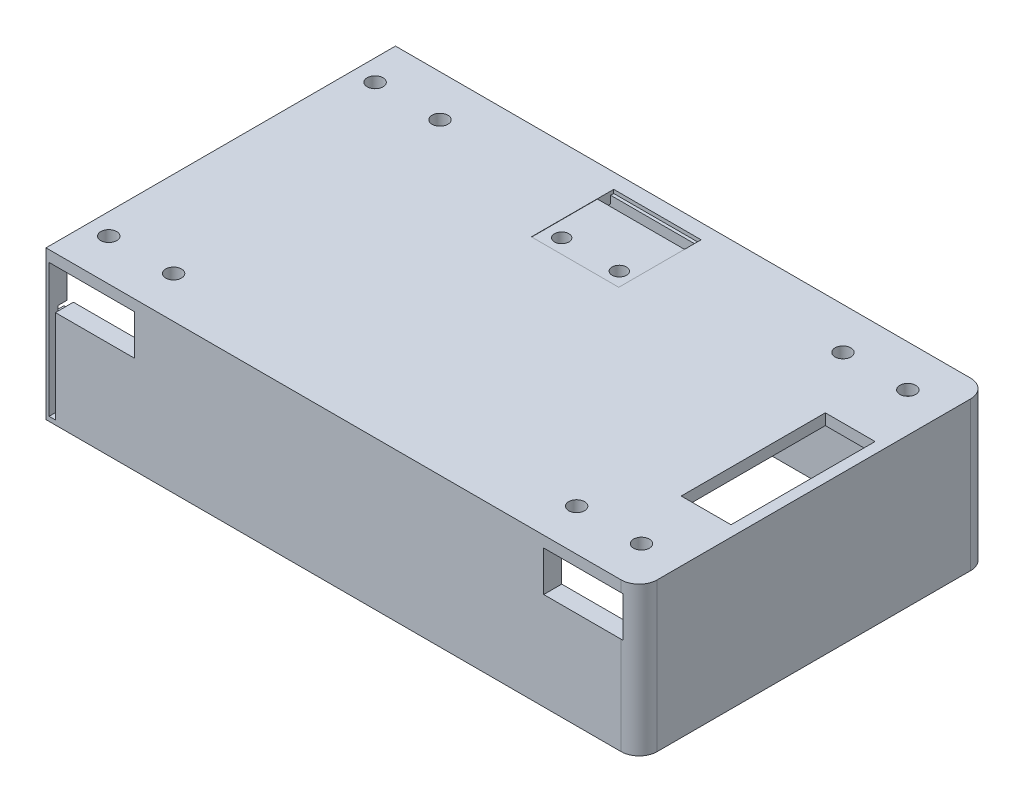
SolidWorks part; units mm, degrees
ref_plane "Alzado" through (0, 0, 0) normal (0, 0, 1) x (1, 0, 0)
ref_plane "Planta" through (0, 0, 0) normal (0, 1, 0) x (1, 0, 0)
ref_plane "Vista lateral" through (0, 0, 0) normal (1, 0, 0) x (0, 0, -1)
sketch "Croquis1" plane through (0, 0, 0) normal (0, 0, 1) x (1, 0, 0)
  line L0 (-8.5, 0) -> (8.5, 0) construction
  line L2 (57, 8.2) -> (57, -26)
  line L3 (57, -26) -> (-57, -26)
  line L4 (-57, 8.2) -> (-57, -26)
  line L5 (30.4, -16) -> (15.6, -16) construction
  line L7 (57, 8.2) -> (-57, 8.2)
  line L8 (47, 0) -> (47, -16) construction
  arc A0 (35, 3.2) -> (34, 3.2) centre (34.5, 3.2) ccw construction
  point P0 (0, 0)
  dimension "D1" = 5
  dimension "D2" = 10
  dimension "D3" = 10
extrude "Saliente-Extruir1" add sketch "Croquis1" against normal blind 97
shell "Vaciado1" thickness 5 removed face at (0, -26, -48.5)
sketch "Croquis2" plane through (0, 0, -97) normal (0, 0, -1) x (-1, 0, 0)
  line L0 (57, 8.2) -> (67.3347, 8.2)
  line L1 (67.3347, 8.2) -> (67.3347, -3.9674)
  line L2 (71.8143, 8.2) -> (71.8143, 10.2965)
  line L3 (67.3347, -26) -> (57, -26)
  line L4 (57, 8.2) -> (57, -26) construction
  line L5 (67.3347, -3.9674) -> (57, -3.9674)
  line L6 (67.3347, 8.2) -> (71.8143, 8.2)
  line L7 (71.8143, 8.2) -> (71.8143, -26)
  line L8 (71.8143, -26) -> (67.3347, -26)
  line L9 (0, 8.2) -> (0, -26) construction
  line L10 (-57, 8.2) -> (57, 8.2) construction
  line L11 (57, -26) -> (-57, -26) construction
  line L12 (71.8143, 10.2965) -> (-71.8143, 10.2965)
  line L13 (67.3347, 8.2) -> (-67.3347, 8.2)
  line L14 (-71.8143, -26) -> (-67.3347, -26)
  line L15 (-71.8143, 8.2) -> (-71.8143, -26)
  line L16 (-67.3347, 8.2) -> (-71.8143, 8.2)
  line L17 (-67.3347, -3.9674) -> (-57, -3.9674)
  line L18 (-67.3347, -26) -> (-57, -26)
  line L19 (-71.8143, 8.2) -> (-71.8143, 10.2965)
  line L20 (-67.3347, 8.2) -> (-67.3347, -3.9674)
  line L21 (-57, 8.2) -> (-67.3347, 8.2)
  point P21 (0, 10.2965)
  line M5 (57, -26) -> (57, 8.2)
  line M6 (57, 8.2) -> (-57, 8.2)
  line M7 (-57, 8.2) -> (-57, -26)
extrude "Saliente-Extruir2" add sketch "Croquis2" against normal through all contours L8 L7 L6 L1 L5 L3 M5 | L19 L16 L13 L0 L6 L2 L12 M6 | L20 L16 L15 L14 L18 L17 M7 region at (0, 9.2483, -97) region at (-65.1466, -12.5368, -97) region at (65.1466, -12.5368, -97)
sketch "Croquis3" plane through (0, -26, 0) normal (0, -1, 0) x (1, 0, 0)
  line L0 (0, 0) -> (0, -97) construction
  line L1 (-71.8143, 0) -> (71.8143, 0) construction
  line L2 (-71.8143, -97) -> (71.8143, -97) construction
  line L3 (-52, -5) -> (-71.8143, -5)
  line L4 (-71.8143, 0) -> (-71.8143, -97) construction
  line L5 (-52, -92) -> (-52, -5) construction
  line L6 (-68.8143, -68.5) -> (-55, -68.5)
  line L7 (-68.8143, -68.5) -> (-68.8143, -28.5)
  line L8 (-68.8143, -28.5) -> (-55, -28.5)
  line L9 (-55, -68.5) -> (-55, -28.5)
  line L10 (-68.8143, -68.5) -> (-55, -28.5) construction
  line L11 (-68.8143, -28.5) -> (-55, -68.5) construction
  line L12 (-71.8143, -48.5) -> (71.8143, -48.5) construction
  line L13 (71.8143, 0) -> (71.8143, -97) construction
  line L14 (68.8143, -28.5) -> (55, -68.5) construction
  line L15 (68.8143, -68.5) -> (55, -28.5) construction
  line L16 (55, -68.5) -> (55, -28.5)
  line L17 (68.8143, -28.5) -> (55, -28.5)
  line L18 (68.8143, -68.5) -> (68.8143, -28.5)
  line L19 (68.8143, -68.5) -> (55, -68.5)
  point P11 (-61.9071, -48.5)
  point P28 (61.9071, -48.5)
  dimension "D1" = 3
  dimension "D2" = 3
  dimension "D3" = 40
extrude "Cortar-Extruir1" cut sketch "Croquis3" against normal up to next contours L6 L9 L8 L7 | L19 L18 L17 L16 region at (-61.9071, -26, -48.5) region at (61.9071, -26, -48.5)
fillet "Redondeo2" radius 5 4 edges at (71.8143, -7.8517, -97) (-71.8143, -7.8517, -97) (71.8143, -7.8517, 0) (-71.8143, -7.8517, 0)
sketch "Croquis5" plane through (-71.8143, 0, 0) normal (-1, 0, 0) x (0, 0, 1)
  line L0 (-5, -10.6991) -> (2.7, -10.6991)
  line L2 (-5, -26) -> (-5, 10.2965) construction
  line L3 (2.7, -10.6991) -> (2.7, -23.7895)
  line L4 (2.7, -23.7895) -> (-5, -23.7895)
  line L5 (-5, -23.7895) -> (-5, -10.6991)
  line L6 (-48.5, -26) -> (-48.5, 10.2965) construction
  line L7 (-5, -26) -> (-92, -26) construction
  line L8 (-5, 10.2965) -> (-92, 10.2965) construction
  line L9 (-92, -23.7895) -> (-92, -10.6991)
  line L10 (-92, -10.6991) -> (-99.7, -10.6991)
  line L11 (-99.7, -10.6991) -> (-99.7, -23.7895)
  line L12 (-99.7, -23.7895) -> (-92, -23.7895)
sketch "Croquis6" plane through (0, 0, -97) normal (0, 0, -1) x (-1, 0, 0)
  line L0 (-67.3347, 8.2) -> (-57, -3.9674) construction
  line L1 (67.3347, 8.2) -> (57, -3.9674) construction
  line L2 (-60.6173, 0) -> (60.6173, 0)
  line L3 (-60.6173, 8.2) -> (-60.6173, -3.9674) construction
  line L4 (-57, 8.2) -> (-66.8143, 8.2) construction
  line L5 (-66.8143, -3.9674) -> (-57, -3.9674) construction
  line L6 (60.6173, 8.2) -> (60.6173, -3.9674) construction
  line L7 (66.8143, 8.2) -> (57, 8.2) construction
  line L8 (66.8143, -3.9674) -> (57, -3.9674) construction
  line L9 (0, 10.2965) -> (0, -26) construction
  line L10 (-66.7673, -3.0837) -> (-54.4673, -3.0837)
  line L11 (-66.7673, -3.0837) -> (-66.7673, 7.3163)
  line L12 (-66.7673, 7.3163) -> (-54.4673, 7.3163)
  line L13 (-54.4673, -3.0837) -> (-54.4673, 7.3163)
  line L14 (-60.6173, 7.3163) -> (-60.6173, -3.0837) construction
  line L15 (-66.7673, 2.1163) -> (-54.4673, 2.1163) construction
  line L16 (66.8143, 10.2965) -> (-66.8143, 10.2965) construction
  line L17 (66.8143, -26) -> (-66.8143, -26) construction
  line L18 (66.7673, 2.1163) -> (54.4673, 2.1163) construction
  line L19 (60.6173, 7.3163) -> (60.6173, -3.0837) construction
  line L20 (60.6173, 8.2) -> (60.6173, -3.9674) construction
  line L21 (67.3347, 8.2) -> (57, -3.9674) construction
  line L22 (54.4673, -3.0837) -> (54.4673, 7.3163)
  line L23 (66.7673, 7.3163) -> (54.4673, 7.3163)
  line L24 (66.7673, -3.0837) -> (66.7673, 7.3163)
  line L25 (66.7673, -3.0837) -> (54.4673, -3.0837)
  point P8 (62.1673, 2.1163)
  point P14 (0, 0)
  point P28 (-60.6173, 2.1163)
  point P46 (60.6173, 2.1163)
  dimension "D1" = 1.55
  dimension "D2" = 12.3
  dimension "D3" = 10.4
extrude "Cortar-Extruir3" cut sketch "Croquis6" against normal through all contours L22 L23 L24 L25 | L11 L12 L13 L10
sketch "Croquis7" plane through (0, 0, -97) normal (0, 0, -1) x (-1, 0, 0)
  line L0 (-57, 7.3163) -> (-57, 8.2)
  line L1 (-54.4673, -3.0837) -> (-66.6673, -3.0837)
  line L2 (-54.4673, -3.0837) -> (-54.4673, 7.325)
  line L3 (-54.4673, 7.325) -> (-66.6673, 7.325)
  line L4 (-66.6673, -3.0837) -> (-66.6673, 7.325)
  line L5 (-57, 8.2) -> (-67.3347, 8.2)
  line L6 (-67.3347, 8.2) -> (-67.3347, -3.9674)
  line L7 (-67.3347, -3.9674) -> (-57, -3.9674)
  line L8 (-57, -3.9674) -> (-57, -3.0837)
  line L9 (57, 7.3163) -> (57, 8.2)
  line L10 (54.4673, -3.0837) -> (66.6673, -3.0837)
  line L11 (54.4673, -3.0837) -> (54.4673, 7.3163)
  line L12 (54.4673, 7.3163) -> (66.6673, 7.3163)
  line L13 (66.6673, -3.0837) -> (66.6673, 7.3163)
  line L14 (57, 8.2) -> (67.3347, 8.2)
  line L15 (67.3347, 8.2) -> (67.3347, -3.9674)
  line L16 (67.3347, -3.9674) -> (57, -3.9674)
  line L17 (57, -3.9674) -> (57, -3.0837)
  line M3 (57, -3.9674) -> (57, -3.0837)
  line M7 (57, 7.3163) -> (57, 8.2)
  line M8 (57, 8.2) -> (66.8143, 8.2)
  line M12 (-66.8143, 8.2) -> (-57, 8.2)
  line M13 (-57, 8.2) -> (-57, 7.3163)
  line M17 (-57, -3.0837) -> (-57, -3.9674)
  line M18 (-57, -3.9674) -> (-66.8143, -3.9674)
  line M22 (66.8143, -3.9674) -> (57, -3.9674)
  dimension "D1" = 12.2
  dimension "D2" = 12.2
extrude "Saliente-Extruir3" add sketch "Croquis7" against normal through all contours L16 L15 L14 L12 L13 L10 M8 M7 M3 M22 | L6 L7 L1 L4 L3 L5 M18 M17 M13 M12 region at (61.8337, 7.4847, -97) region at (-57.1596, 7.7582, -97)
sketch "Croquis8" plane through (0, 10.2965, 0) normal (0, 1, 0) x (1, 0, 0)
  line L1 (-68.8143, 68.5) -> (-55, 68.5)
  line L2 (-68.8143, 68.5) -> (-68.8143, 28.5)
  line L3 (-68.8143, 28.5) -> (-55, 28.5)
  line L4 (-55, 68.5) -> (-55, 28.5)
  line L5 (55, 68.5) -> (68.8143, 68.5)
  line L6 (55, 68.5) -> (55, 28.5)
  line L7 (55, 28.5) -> (68.8143, 28.5)
  line L8 (68.8143, 68.5) -> (68.8143, 28.5)
extrude "Cortar-Extruir4" cut sketch "Croquis8" against normal through all
sketch "Croquis9" plane through (0, 3.2, 0) normal (0, -1, 0) x (1, 0, 0)
  line L0 (52, -92) -> (52, -5) construction
  line L1 (-52, -5) -> (52, -5)
  line L2 (-52, -5) -> (-52, -92)
  line L3 (-52, -92) -> (52, -92)
  line L4 (52, -5) -> (52, -92)
extrude "Cortar-Extruir5" cut sketch "Croquis9" against normal blind 10
ref_plane "Plano1" through (54.4673, -3.0837, -97) normal (-1, 0, 0) x (0, 0, 1)
sketch "Croquis11" plane through (0, -26, 0) normal (0, -1, 0) x (1, 0, 0)
  line L1 (55, -28.5) -> (53.5, -28.5)
  line L2 (55, -28.5) -> (55, -68.4995)
  line L3 (55, -68.4995) -> (53.5, -68.4995)
  line L4 (53.5, -28.5) -> (53.5, -68.4995)
  line L5 (-55, -68.5) -> (-53.5, -68.5)
  line L6 (-55, -68.5) -> (-55, -28.5)
  line L7 (-55, -28.5) -> (-53.5, -28.5)
  line L8 (-53.5, -68.5) -> (-53.5, -28.5)
  dimension "D1" = 1.5
  dimension "D2" = 1.5
extrude "Cortar-Extruir6" cut sketch "Croquis11" against normal up to vertex (33.3163 mm away) up to point (-55, 7.3163, -28.5)
sketch "Croquis13" plane through (0, -26, 0) normal (0, -1, 0) x (1, 0, 0)
  line L1 (-68.8143, -28.5) -> (-53.5, -28.5)
  line L2 (-68.8143, -28.5) -> (-68.8143, -24)
  line L3 (-68.8143, -24) -> (-53.5, -24)
  line L4 (-53.5, -28.5) -> (-53.5, -24)
  line L5 (-68.8143, -68.5) -> (-53.5, -68.5)
  line L6 (-68.8143, -68.5) -> (-68.8143, -73)
  line L7 (-68.8143, -73) -> (-53.5, -73)
  line L8 (-53.5, -68.5) -> (-53.5, -73)
  line L9 (53.5, -28.5) -> (68.8143, -28.5)
  line L10 (53.5, -28.5) -> (53.5, -24)
  line L11 (53.5, -24) -> (68.8143, -24)
  line L12 (68.8143, -28.5) -> (68.8143, -24)
  line L13 (53.5, -68.4995) -> (68.8143, -68.4995)
  line L14 (53.5, -68.4995) -> (53.5, -72.9995)
  line L15 (53.5, -72.9995) -> (68.8143, -72.9995)
  line L16 (68.8143, -68.4995) -> (68.8143, -72.9995)
  dimension "D1" = 4.5
  dimension "D2" = 4.5
  dimension "D3" = 4.5
  dimension "D4" = 4.5
extrude "Cortar-Extruir7" cut sketch "Croquis13" against normal up to surface (33.3163 mm away) up to face at (-58.4616, 7.3163, -48.5)
sketch "Croquis14" plane through (-55, 0, 0) normal (-1, 0, 0) x (0, 0, 1)
  line L4 (-68.5, 10.2965) -> (-68.5, 7.3163)
  line L5 (-68.5, 7.3163) -> (-28.5, 7.3163)
  line L6 (-28.5, 7.3163) -> (-28.5, 10.2965)
  line L7 (-28.5, 10.2965) -> (-68.5, 10.2965)
  line L8 (-68.5, 10.2965) -> (-68.5, 7.3163)
  line L9 (-68.5, 7.3163) -> (-28.5, 7.3163)
  line L10 (-28.5, 7.3163) -> (-28.5, 10.2965)
  line L11 (-28.5, 10.2965) -> (-68.5, 10.2965)
  dimension "D1" = 0
extrude "Saliente-Extruir4" add sketch "Croquis14" along normal blind 15.4989
sketch "Croquis16" plane through (-71.8143, 0, 0) normal (-1, 0, 0) x (0, 0, 1)
  line L0 (-5, 10.2965) -> (-98.4159, 10.2965)
  line L1 (-98.4159, 10.2965) -> (-98.4159, -27.1379)
  line L2 (-98.4159, -27.1379) -> (0, -27.1379)
  line L3 (0, -27.1379) -> (0, 10.2965)
  line L4 (0, 10.2965) -> (-5, 10.2965)
extrude "Cortar-Extruir8" cut sketch "Croquis16" against normal blind 20.4989
sketch "Croquis19" plane through (-51.3154, 0, 0) normal (-1, 0, 0) x (0, 0, 1)
  line L0 (0, -4.4636) -> (-5, -4.4636)
  line L1 (-92, -4.4636) -> (-97, -4.4636)
  line L2 (-5, -26) -> (-5, 10.2965) construction
  line L3 (0, 10.2965) -> (-5, 10.2965)
  line L4 (0, -26) -> (0, 10.2965)
  line L5 (0, 10.2965) -> (-5, 10.2965)
  line L6 (-5, 10.2965) -> (-5, -26)
  line L7 (-5, -26) -> (0, -26)
  line L8 (0, -26) -> (0, -4.4636)
  line L10 (-5, -4.4636) -> (-5, -26)
  line L11 (-5, -26) -> (0, -26)
  line L12 (0, 10.2965) -> (0, 7.9471)
  line L13 (-97, -26) -> (-92, -26)
  line L14 (-92, -26) -> (-92, 10.2965)
  line L15 (-92, 10.2965) -> (-97, 10.2965)
  line L16 (-97, 10.2965) -> (-97, -26)
  line L17 (-97, -26) -> (-92, -26)
  line L18 (-92, -26) -> (-92, -4.4636)
  line L20 (-97, -4.4636) -> (-97, -26)
  line L21 (0, 7.9471) -> (-5, 7.9471)
  line L22 (-5, 10.2965) -> (-5, 7.9471)
  line L23 (-97, -26) -> (-97, 10.2965) construction
  line L24 (-92, 10.2965) -> (-97, 10.2965)
  line L25 (-92, 10.2965) -> (-92, 7.9471)
  line L26 (-92, 7.9471) -> (-97, 7.9471)
  line L27 (-97, 10.2965) -> (-97, 7.9471)
  dimension "D1" = 0
  dimension "D2" = 0
extrude "Saliente-Extruir5" add sketch "Croquis19" along normal blind 22
sketch "Croquis20" plane through (-73.3154, 0, 0) normal (-1, 0, 0) x (0, 0, 1)
  line L0 (-5, -26) -> (0, -26) construction
  line L1 (0, 10.2965) -> (-5, 10.2965)
  line L2 (0, 10.2965) -> (0, -26)
  line L3 (0, -26) -> (-5, -26)
  line L4 (-5, 10.2965) -> (-5, -26)
  line L5 (-5, -4.4636) -> (-5, -26) construction
  line L7 (-92, 10.2965) -> (-97, 10.2965)
  line L8 (-92, 10.2965) -> (-92, -26)
  line L9 (-92, -26) -> (-97, -26)
  line L10 (-97, 10.2965) -> (-97, -26)
extrude "Saliente-Extruir6" add sketch "Croquis20" along normal blind 19.5
sketch "Croquis21" plane through (52, 0, 0) normal (-1, 0, 0) x (0, 0, 1)
  line L1 (-5, 10.2965) -> (-92, 10.2965)
  line L2 (-5, 10.2965) -> (-5, 7.9471)
  line L3 (-5, 7.9471) -> (-92, 7.9471)
  line L4 (-92, 10.2965) -> (-92, 7.9471)
extrude "Saliente-Extruir7" add sketch "Croquis21" along normal up to surface (144.8154 mm away) up to face at (-92.8154, -7.8517, -2.5)
sketch "Croquis23" plane through (0, 0, 0) normal (0, 0, 1) x (1, 0, 0)
  line L0 (-92.8154, 10.2965) -> (-92.8154, 7.8837) construction
  line L1 (-92.8154, -26) -> (-92.8154, 10.2965) construction
  line L3 (-92.3813, 9.0724) -> (-90.9831, 9.0724)
  line L4 (-92.3813, 9.0724) -> (-92.3813, -24.6285)
  line L5 (-92.3813, -24.6285) -> (-90.9831, -24.6285)
  line L6 (-90.9831, 9.0724) -> (-90.9831, -24.6285)
extrude "Cortar-Extruir9" cut sketch "Croquis23" against normal blind 95.5
sketch "Croquis24" plane through (0, 10.2965, 0) normal (0, 1, 0) x (1, 0, 0)
  line L0 (-92.8154, 48.5) -> (-89.7623, 48.5) construction
  line L1 (-92.8154, 0) -> (-92.8154, 97) construction
  line L2 (-89.7623, 37.3943) -> (-89.7623, 59.6057)
  line L3 (-89.7623, 59.6057) -> (-67.2686, 59.6057)
  line L4 (-67.2686, 59.6057) -> (-67.2686, 37.3943)
  line L5 (-67.2686, 37.3943) -> (-89.7623, 37.3943)
  point P7 (-89.7623, 48.5)
extrude "Cortar-Extruir10" cut sketch "Croquis24" against normal blind 1.5
sketch "Croquis25" plane through (0, 8.7965, 0) normal (0, 1, 0) x (1, 0, 0)
  line L0 (-89.7623, 59.6057) -> (-89.7623, 37.3943) construction
  line L1 (-89.7623, 40.2654) -> (-84.2178, 40.2654)
  line L2 (-89.7623, 40.2654) -> (-89.7623, 57.0137)
  line L3 (-89.7623, 57.0137) -> (-84.2178, 57.0137)
  line L4 (-84.2178, 40.2654) -> (-84.2178, 57.0137)
extrude "Cortar-Extruir11" cut sketch "Croquis25" against normal blind 1.5
sketch "Croquis26" plane through (-89.7623, 0, 0) normal (1, 0, 0) x (0, 0, -1)
  line L8 (59.6057, 10.2965) -> (37.3943, 10.2965)
  line L9 (37.3943, 10.2965) -> (37.3943, 8.7965)
  line L10 (37.3943, 8.7965) -> (40.2654, 8.7965)
  line L11 (40.2654, 8.7965) -> (40.2654, 7.9471)
  line L12 (40.2654, 7.9471) -> (57.0137, 7.9471)
  line L13 (57.0137, 7.9471) -> (57.0137, 8.7965)
  line L14 (57.0137, 8.7965) -> (59.6057, 8.7965)
  line L15 (59.6057, 8.7965) -> (59.6057, 10.2965)
  line L16 (59.6057, 10.2965) -> (37.3943, 10.2965)
  line L17 (37.3943, 10.2965) -> (37.3943, 8.7965)
  line L18 (37.3943, 8.7965) -> (40.2654, 8.7965)
  line L19 (40.2654, 8.7965) -> (40.2654, 7.9471)
  line L20 (40.2654, 7.9471) -> (57.0137, 7.9471)
  line L21 (57.0137, 7.9471) -> (57.0137, 8.7965)
  line L22 (57.0137, 8.7965) -> (59.6057, 8.7965)
  line L23 (59.6057, 8.7965) -> (59.6057, 10.2965)
  dimension "D1" = 0
extrude "Saliente-Extruir8" add sketch "Croquis26" along normal blind 46
sketch "Croquis27" plane through (0, 10.2965, 0) normal (0, 1, 0) x (1, 0, 0)
  line L0 (-90.9831, 92) -> (-73.3154, 92) construction
  line L1 (-82.5488, 92) -> (-60.5488, 92)
  line L2 (-82.5488, 92) -> (-82.5488, 70)
  line L3 (-82.5488, 70) -> (-60.5488, 70)
  line L4 (-60.5488, 92) -> (-60.5488, 70)
  dimension "D1" = 22
  dimension "D2" = 22
extrude "Cortar-Extruir12" cut sketch "Croquis27" against normal blind 1
sketch "Croquis28" plane through (0, 9.2965, 0) normal (0, 1, 0) x (1, 0, 0)
  line L1 (-60.9342, 91.7) -> (-82.0403, 91.7)
  line L2 (-60.9342, 91.7) -> (-60.9342, 87.3693)
  line L3 (-60.9342, 87.3693) -> (-82.0403, 87.3693)
  line L4 (-82.0403, 91.7) -> (-82.0403, 87.3693)
extrude "Cortar-Extruir14" cut sketch "Croquis28" against normal blind 1.5
sketch "Croquis29" plane through (-90.9831, 0, 0) normal (-1, 0, 0) x (0, 0, 1)
  line L8 (-92, 7.9471) -> (-5, 7.9471)
  line L9 (-5, 7.9471) -> (-5, -24.6285)
  line L10 (-5, -24.6285) -> (0, -24.6285)
  line L11 (0, -24.6285) -> (0, 9.0724)
  line L12 (0, 9.0724) -> (-95.5, 9.0724)
  line L13 (-95.5, 9.0724) -> (-95.5, -24.6285)
  line L14 (-95.5, -24.6285) -> (-92, -24.6285)
  line L15 (-92, -24.6285) -> (-92, 7.9471)
  line L16 (-92, 7.9471) -> (-5, 7.9471)
  line L17 (-5, 7.9471) -> (-5, -24.6285)
  line L18 (-5, -24.6285) -> (0, -24.6285)
  line L19 (0, -24.6285) -> (0, 9.0724)
  line L20 (0, 9.0724) -> (-95.5, 9.0724)
  line L21 (-95.5, 9.0724) -> (-95.5, -24.6285)
  line L22 (-95.5, -24.6285) -> (-92, -24.6285)
  line L23 (-92, -24.6285) -> (-92, 7.9471)
  dimension "D1" = 0
extrude "Saliente-Extruir9" add sketch "Croquis29" along normal up to surface (1.8323 mm away) up to face at (-92.8154, -8.4391, -48.5)
sketch "Croquis30" plane through (0, 7.9471, 0) normal (0, -1, 0) x (1, 0, 0)
  line L0 (-26.9383, -87.6693) -> (-5.8322, -87.6693)
  line L1 (-82.0403, -87.3693) -> (-60.9342, -87.3693)
  line L2 (-82.0403, -87.3693) -> (-82.0403, -91.7)
  line L3 (-82.0403, -91.7) -> (-60.9342, -91.7)
  line L4 (-60.9342, -87.3693) -> (-60.9342, -91.7)
  line L6 (-26.9383, -92) -> (-5.8322, -92)
  line L8 (-51.3154, -92) -> (52, -92) construction
  line L9 (-26.9383, -92) -> (-26.9383, -87.6693)
  line L10 (-5.8322, -87.6693) -> (-5.8322, -92)
extrude "Cortar-Extruir15" cut sketch "Croquis30" against normal blind 10
sketch "Croquis31" plane through (0, 10.2965, 0) normal (0, 1, 0) x (1, 0, 0)
  line L1 (-82.5488, 92) -> (-60.5488, 92)
  line L2 (-82.5488, 92) -> (-82.5488, 70)
  line L3 (-82.5488, 70) -> (-60.5488, 70)
  line L4 (-60.5488, 92) -> (-60.5488, 70)
  line L5 (-28.087, 92.8509) -> (-3.838, 92.8509)
  line L6 (-28.087, 92.8509) -> (-28.087, 70)
  line L7 (-28.087, 70) -> (-3.838, 70)
  line L8 (-3.838, 92.8509) -> (-3.838, 70)
  dimension "D1" = 22
  dimension "D2" = 22
extrude "Cortar-Extruir16" cut sketch "Croquis31" against normal blind 1
sketch "Croquis32" plane through (0, 7.9471, 0) normal (0, -1, 0) x (1, 0, 0)
  line L0 (-92.8154, -92) -> (-73.3154, -92) construction
  line L1 (-83.0654, -92) -> (-55.1323, -92)
  line L2 (-83.0654, -92) -> (-83.0654, -55.3525)
  line L3 (-83.0654, -55.3525) -> (-55.1323, -55.3525)
  line L4 (-55.1323, -92) -> (-55.1323, -55.3525)
extrude "Saliente-Extruir10" add sketch "Croquis32" against normal up to surface (2.3495 mm away) up to face at (-15.9625, 10.2965, -81.4255)
sketch "Croquis33" plane through (0, 7.9471, 0) normal (0, -1, 0) x (1, 0, 0)
  line L0 (52, -5) -> (-92.8154, -5)
  dimension "D1" = 144.8154
sketch "Croquis36" plane through (-92.8154, 0, 0) normal (-1, 0, 0) x (0, 0, 1)
  line L8 (-94.5, -6.1159) -> (-94.5, -4.3783) construction
  line L18 (-2.5, -6.1159) -> (-2.5, -4.3783) construction
  line L21 (-2.5, -6.1159) -> (-94.5, -6.1159)
  line L26 (-2.5, -6.1159) -> (-94.5, -6.1159)
  line L30 (-2.5, -6.1159) -> (-2.5, -4.3783)
  line L31 (-2.5, -4.3783) -> (-94.5, -4.3783)
  line L32 (-94.5, -6.1159) -> (-94.5, -4.3783)
  line M11 (-92, -26) -> (-92, 7.9471)
  line M13 (-5, 7.9471) -> (-5, -26)
extrude "Cortar-Extruir17" cut sketch "Croquis36" against normal blind 147 contours L31 L21 M13 M11 | L30 L31 L21 M13 | L32 L21 L31 M11 region at (-92.8154, -5.2471, -3.75) region at (-92.8154, -5.2471, -48.5) region at (-92.8154, -5.2471, -93.25)
sketch "Croquis37" plane through (0, -26, 0) normal (0, -1, 0) x (1, 0, 0)
  line L0 (68.8143, -24) -> (53.5, -24) construction
  line L1 (53.5, -24) -> (53.5, -72.9995) construction
  line L2 (53.5, -72.9995) -> (68.8143, -72.9995) construction
  line L3 (68.8143, -72.9995) -> (68.8143, -24) construction
  line L4 (68.8143, -24) -> (53.5, -24)
  line L5 (53.5, -24) -> (53.5, -72.9995)
  line L6 (53.5, -72.9995) -> (68.8143, -72.9995)
  line L7 (68.8143, -72.9995) -> (68.8143, -24)
  line L8 (66.8143, 0) -> (-92.8154, 0)
  line L9 (-92.8154, 0) -> (-92.8154, -5)
  line L10 (-92.8154, -5) -> (52, -5)
  line L11 (52, -5) -> (52, -92)
  line L12 (52, -92) -> (-92.8154, -92)
  line L13 (-92.8154, -92) -> (-92.8154, -97)
  line L14 (-92.8154, -97) -> (66.8143, -97)
  line L15 (71.8143, -92) -> (71.8143, -5)
  line L16 (66.8143, 0) -> (-92.8154, 0)
  line L17 (-92.8154, 0) -> (-92.8154, -5)
  line L18 (-92.8154, -5) -> (52, -5)
  line L19 (52, -5) -> (52, -92)
  line L20 (52, -92) -> (-92.8154, -92)
  line L21 (-92.8154, -92) -> (-92.8154, -97)
  line L22 (-92.8154, -97) -> (66.8143, -97)
  line L23 (71.8143, -92) -> (71.8143, -5)
  arc A2 (66.8143, -97) -> (71.8143, -92) centre (66.8143, -92) ccw
  arc A3 (71.8143, -5) -> (66.8143, 0) centre (66.8143, -5) ccw
  arc A4 (66.8143, -97) -> (71.8143, -92) centre (66.8143, -92) ccw
  arc A5 (71.8143, -5) -> (66.8143, 0) centre (66.8143, -5) ccw
  dimension "D1" = 0
extrude "Saliente-Extruir11" add sketch "Croquis37" along normal blind 5
sketch "Croquis38" plane through (0, -31, 0) normal (0, -1, 0) x (1, 0, 0)
  line L0 (52, -92) -> (-92.8154, -92) construction
  line L1 (52, -5) -> (46, -5)
  line L2 (52, -5) -> (52, -11)
  line L3 (52, -11) -> (46, -11)
  line L4 (46, -5) -> (46, -11)
  line L5 (52, -92) -> (46, -92)
  line L6 (52, -92) -> (52, -86)
  line L7 (52, -86) -> (46, -86)
  line L8 (46, -92) -> (46, -86)
  line L9 (-72.9049, -92) -> (-66.9049, -92)
  line L10 (-72.9049, -92) -> (-72.9049, -86)
  line L11 (-72.9049, -86) -> (-66.9049, -86)
  line L12 (-66.9049, -92) -> (-66.9049, -86)
  line L13 (-72.9049, -86) -> (-73.3154, -5) construction
  line L15 (-73.3154, -5) -> (-67.3154, -5)
  line L16 (-73.3154, -5) -> (-73.3154, -11)
  line L17 (-73.3154, -11) -> (-67.3154, -11)
  line L18 (-67.3154, -5) -> (-67.3154, -11)
  circle A1 centre (49, -8) radius 1.5
  circle A2 centre (49, -89) radius 1.5
  circle A3 centre (-70.3154, -8) radius 1.5
  dimension "D1" = 3
  dimension "D6" = 6
  dimension "D2" = 6
  dimension "D3" = 6
  dimension "D4" = 6
  dimension "D5" = 6
  dimension "D7" = 6
  dimension "D8" = 6
  dimension "D9" = 6
extrude "Saliente-Extruir12" add sketch "Croquis38" against normal blind 1.5
sketch "Croquis39" plane through (0, -31, 0) normal (0, -1, 0) x (1, 0, 0)
  circle A0 centre (-69.8502, -89.2089) radius 1.5
extrude "Cortar-Extruir18" cut sketch "Croquis39" against normal blind 1.5
sketch "Croquis40" plane through (0, 0, 0) normal (0, 0, 1) x (1, 0, 0)
  line L1 (-91.9601, 9.2181) -> (-90.2101, 9.2181)
  line L2 (-91.9601, 9.2181) -> (-91.9601, -29.7819)
  line L3 (-91.9601, -29.7819) -> (-90.2101, -29.7819)
  line L4 (-90.2101, 9.2181) -> (-90.2101, -29.7819)
  dimension "D1" = 1.75
  dimension "D2" = 39
extrude "Cortar-Extruir19" cut sketch "Croquis40" against normal blind 95.5
sketch "Croquis41" plane through (52, 0, 0) normal (-1, 0, 0) x (0, 0, 1)
  line L4 (-92, 7.9471) -> (-92, -4.3783)
  line L5 (-92, -4.3783) -> (-5, -4.3783)
  line L6 (-5, -4.3783) -> (-5, 7.9471)
  line L7 (-5, 7.9471) -> (-92, 7.9471)
  line L8 (-92, 7.9471) -> (-92, -4.3783)
  line L9 (-92, -4.3783) -> (-5, -4.3783)
  line L10 (-5, -4.3783) -> (-5, 7.9471)
  line L11 (-5, 7.9471) -> (-92, 7.9471)
  dimension "D1" = 0
extrude "Cortar-Extruir20" cut sketch "Croquis41" against normal blind 10
sketch "Croquis42" plane through (0, 0, 0) normal (0, 0, 1) x (1, 0, 0)
  line L6 (-73.3154, 7.9471) -> (-51.3154, 7.9471)
  line L7 (-73.3154, 7.9471) -> (-73.3154, -4.4636)
  line L8 (-73.3154, -4.4636) -> (-51.3154, -4.4636)
  line L9 (-51.3154, 7.9471) -> (-51.3154, -4.4636)
  line L10 (54.4673, 7.3163) -> (66.6673, 7.3163)
  line L11 (54.4673, 7.3163) -> (54.4673, -3.0837)
  line L12 (54.4673, -3.0837) -> (66.6673, -3.0837)
  line L13 (66.6673, 7.3163) -> (66.6673, -3.0837)
extrude "Saliente-Extruir13" add sketch "Croquis42" against normal up to surface (5 mm away) up to face at (-92.3878, 1.7844, -5)
sketch "Croquis43" plane through (0, 0, 0) normal (0, 0, 1) x (1, 0, 0)
  line L0 (67.3347, -3.9674) -> (67.3347, -3.7226)
  line L1 (67.3347, 8.2) -> (45.3347, 8.2)
  line L2 (67.3347, 8.2) -> (67.3347, -3.7226)
  line L4 (45.3347, 8.2) -> (45.3347, -3.7226)
  line L5 (67.3347, -3.9674) -> (45.3347, -3.9674)
  line L6 (45.3347, -3.9674) -> (45.3347, -3.7226)
  line L7 (45.3347, 8.2) -> (-90.2101, 9.2181) construction
  line L9 (-90.2101, 9.2181) -> (-68.2101, 9.2181)
  line L10 (-90.2101, 9.2181) -> (-90.2101, 0)
  line L11 (-90.2101, 0) -> (-68.2101, 0)
  line L12 (-68.2101, 9.2181) -> (-68.2101, 0)
  dimension "D1" = 22
  dimension "D2" = 22
extrude "Cortar-Extruir21" cut sketch "Croquis43" against normal up to surface (97 mm away) up to face at (27.037, -4.1177, -97)
sketch "Croquis44" plane through (0, 0, -97) normal (0, 0, -1) x (-1, 0, 0)
  line L0 (68.2101, 7.9471) -> (68.2101, 0)
  line L1 (68.2101, 0) -> (73.3154, 0)
  line L2 (68.2101, 7.9471) -> (51.3154, 7.9471)
  line L3 (51.3154, 7.9471) -> (51.3154, -4.4636)
  line L6 (73.3154, -4.4636) -> (51.3154, -4.4636) construction
  line L7 (73.3154, -4.4636) -> (51.3154, -4.4636) construction
  line L8 (51.3154, -4.4636) -> (73.3154, -4.3783)
  line L9 (73.3154, -4.3783) -> (73.3154, 0)
extrude "Saliente-Extruir14" add sketch "Croquis44" against normal up to surface (5 mm away) up to face at (-92.3878, 1.7844, -92)
sketch "Croquis45" plane through (0, 9.2181, 0) normal (0, -1, 0) x (1, 0, 0)
  circle A0 centre (-86.9308, -85.4655) radius 1.264
sketch "Croquis46" plane through (0, 9.2181, 0) normal (0, -1, 0) x (1, 0, 0)
  line L0 (-86.9308, -85.4655) -> (-68.9308, -85.4655) construction
  line L1 (-92.8154, -48.5) -> (-59.9308, -48.5) construction
  line L2 (-92.8154, -5) -> (-92.8154, -92) construction
  circle A0 centre (-68.9308, -85.4655) radius 2.2
  circle A1 centre (-86.9308, -85.4655) radius 2.2
  circle A2 centre (-68.9308, -11.5345) radius 2.2
  circle A3 centre (-86.9308, -11.5345) radius 2.2
  dimension "D1" = 18
extrude "Cortar-Extruir22" cut sketch "Croquis46" against normal up to surface (1.0784 mm away) up to face at (-15.9625, 10.2965, -81.4255)
sketch "Croquis47" plane through (0, 7.9471, 0) normal (0, -1, 0) x (1, 0, 0)
  line L8 (-68.2101, -5) -> (-68.2101, -92)
  line L9 (-68.2101, -92) -> (-26.9383, -92)
  line L10 (-26.9383, -92) -> (-26.9383, -87.6693)
  line L11 (-26.9383, -87.6693) -> (-5.8322, -87.6693)
  line L12 (-5.8322, -87.6693) -> (-5.8322, -92)
  line L13 (-5.8322, -92) -> (45.3347, -92)
  line L14 (45.3347, -92) -> (45.3347, -5)
  line L15 (45.3347, -5) -> (-68.2101, -5)
  line L16 (-68.2101, -5) -> (-68.2101, -92)
  line L17 (-68.2101, -92) -> (-26.9383, -92)
  line L18 (-26.9383, -92) -> (-26.9383, -87.6693)
  line L19 (-26.9383, -87.6693) -> (-5.8322, -87.6693)
  line L20 (-5.8322, -87.6693) -> (-5.8322, -92)
  line L21 (-5.8322, -92) -> (45.3347, -92)
  line L22 (45.3347, -92) -> (45.3347, -5)
  line L23 (45.3347, -5) -> (-68.2101, -5)
  dimension "D1" = 0
extrude "Cortar-Extruir23" cut sketch "Croquis47" against normal up to surface (1.2711 mm away) up to face at (-86.9308, 9.2181, -87.6655)
sketch "Croquis48" plane through (0, 9.2181, 0) normal (0, -1, 0) x (1, 0, 0)
  line L0 (-13.0006, 0) -> (-13.0006, -82.2778) construction
  line L1 (66.8143, 0) -> (-92.8154, 0) construction
  circle A0 centre (42.9297, -85.4655) radius 2.2
  circle A1 centre (-68.9308, -85.4655) radius 2.2
  circle A2 centre (-68.9308, -85.4655) radius 2.2
  circle A3 centre (-86.9308, -11.5345) radius 2.2
  circle A4 centre (-86.9308, -11.5345) radius 2.2
  circle A5 centre (-86.9308, -85.4655) radius 2.2
  circle A6 centre (-86.9308, -85.4655) radius 2.2
  circle A7 centre (-68.9308, -11.5345) radius 2.2
  circle A8 centre (-68.9308, -11.5345) radius 2.2
  circle A9 centre (60.9297, -85.4655) radius 2.2
  circle A10 centre (42.9297, -11.5345) radius 2.2
  circle A11 centre (60.9297, -11.5345) radius 2.2
  dimension "D1" = 0
  dimension "D2" = 0
  dimension "D3" = 0
  dimension "D4" = 0
extrude "Cortar-Extruir24" cut sketch "Croquis48" against normal up to surface (1.0784 mm away) up to face at (-86.9308, 10.2965, -83.2655)
sketch "Croquis49" plane through (0, 8.2, 0) normal (0, -1, 0) x (1, 0, 0)
  line L10 (67.3347, -68.5) -> (55, -68.5)
  line L11 (55, -68.5) -> (55, -28.5)
  line L12 (55, -28.5) -> (67.3347, -28.5)
  line L13 (67.3347, -28.5) -> (67.3347, -0.0272)
  line L14 (66.8143, 0) -> (45.3347, 0)
  line L15 (45.3347, 0) -> (45.3347, -5)
  line L16 (45.3347, -5) -> (45.3347, -92)
  line L17 (45.3347, -92) -> (45.3347, -97)
  line L18 (45.3347, -97) -> (66.8143, -97)
  line L19 (67.3347, -96.9728) -> (67.3347, -68.5)
  line L20 (67.3347, -68.5) -> (55, -68.5)
  line L21 (55, -68.5) -> (55, -28.5)
  line L22 (55, -28.5) -> (67.3347, -28.5)
  line L23 (67.3347, -28.5) -> (67.3347, -0.0272)
  line L24 (66.8143, 0) -> (45.3347, 0)
  line L25 (45.3347, 0) -> (45.3347, -5)
  line L26 (45.3347, -5) -> (45.3347, -92)
  line L27 (45.3347, -92) -> (45.3347, -97)
  line L28 (45.3347, -97) -> (66.8143, -97)
  line L29 (67.3347, -96.9728) -> (67.3347, -68.5)
  arc A2 (67.3347, -0.0272) -> (66.8143, 0) centre (66.8143, -5) ccw
  arc A3 (66.8143, -97) -> (67.3347, -96.9728) centre (66.8143, -92) ccw
  arc A4 (67.3347, -0.0272) -> (66.8143, 0) centre (66.8143, -5) ccw
  arc A5 (66.8143, -97) -> (67.3347, -96.9728) centre (66.8143, -92) ccw
  dimension "D1" = 0
extrude "Cortar-Extruir25" cut sketch "Croquis49" against normal up to surface (1.0181 mm away) up to face at (42.9297, 9.2181, -83.2655)
sketch "Croquis50" plane through (0, 0, -97) normal (0, 0, -1) x (-1, 0, 0)
  line L1 (90.2101, 9.2181) -> (68.2101, 9.2181)
  line L2 (90.2101, 9.2181) -> (90.2101, -3.9674)
  line L3 (90.2101, -3.9674) -> (68.2101, -3.9674)
  line L4 (68.2101, 9.2181) -> (68.2101, -3.9674)
  line L6 (-67.3347, 9.2181) -> (-45.3347, 9.2181)
  line L7 (-67.3347, 9.2181) -> (-67.3347, -3.9674)
  line L8 (-67.3347, -3.9674) -> (-45.3347, -3.9674)
  line L9 (-45.3347, 9.2181) -> (-45.3347, -3.9674)
  dimension "D1" = 22
extrude "Cortar-Extruir26" cut sketch "Croquis50" against normal up to surface (97 mm away) up to face at (-83.4601, -6.8546, 0)
sketch "Croquis51" plane through (0, 9.2181, 0) normal (0, -1, 0) x (1, 0, 0)
  line L22 (45.3347, -5) -> (-68.2101, -5)
  line L23 (-68.2101, -5) -> (-68.2101, 0)
  line L24 (-68.2101, 0) -> (-91.9601, 0)
  line L25 (-91.9601, 0) -> (-91.9601, -95.5)
  line L26 (-91.9601, -95.5) -> (-90.2101, -95.5)
  line L27 (-90.2101, -95.5) -> (-90.2101, -97)
  line L28 (-90.2101, -97) -> (-68.2101, -97)
  line L29 (-68.2101, -97) -> (-68.2101, -92)
  line L30 (-68.2101, -92) -> (-26.9383, -92)
  line L31 (-26.9383, -92) -> (-26.9383, -87.6693)
  line L32 (-26.9383, -87.6693) -> (-5.8322, -87.6693)
  line L33 (-5.8322, -87.6693) -> (-5.8322, -92)
  line L34 (-5.8322, -92) -> (45.3347, -92)
  line L35 (45.3347, -92) -> (45.3347, -97)
  line L36 (45.3347, -97) -> (66.8143, -97)
  line L37 (67.3347, -96.9728) -> (67.3347, -68.5)
  line L38 (67.3347, -68.5) -> (55, -68.5)
  line L39 (55, -68.5) -> (55, -28.5)
  line L40 (55, -28.5) -> (67.3347, -28.5)
  line L41 (67.3347, -28.5) -> (67.3347, -0.0272)
  line L42 (66.8143, 0) -> (45.3347, 0)
  line L43 (45.3347, 0) -> (45.3347, -5)
  line L44 (45.3347, -5) -> (-68.2101, -5)
  line L45 (-68.2101, -5) -> (-68.2101, 0)
  line L46 (-68.2101, 0) -> (-91.9601, 0)
  line L47 (-91.9601, 0) -> (-91.9601, -95.5)
  line L48 (-91.9601, -95.5) -> (-90.2101, -95.5)
  line L49 (-90.2101, -95.5) -> (-90.2101, -97)
  line L50 (-90.2101, -97) -> (-68.2101, -97)
  line L51 (-68.2101, -97) -> (-68.2101, -92)
  line L52 (-68.2101, -92) -> (-26.9383, -92)
  line L53 (-26.9383, -92) -> (-26.9383, -87.6693)
  line L54 (-26.9383, -87.6693) -> (-5.8322, -87.6693)
  line L55 (-5.8322, -87.6693) -> (-5.8322, -92)
  line L56 (-5.8322, -92) -> (45.3347, -92)
  line L57 (45.3347, -92) -> (45.3347, -97)
  line L58 (45.3347, -97) -> (66.8143, -97)
  line L59 (67.3347, -96.9728) -> (67.3347, -68.5)
  line L60 (67.3347, -68.5) -> (55, -68.5)
  line L61 (55, -68.5) -> (55, -28.5)
  line L62 (55, -28.5) -> (67.3347, -28.5)
  line L63 (67.3347, -28.5) -> (67.3347, -0.0272)
  line L64 (66.8143, 0) -> (45.3347, 0)
  line L65 (45.3347, 0) -> (45.3347, -5)
  arc A2 (66.8143, -97) -> (67.3347, -96.9728) centre (66.8143, -92) ccw
  arc A3 (67.3347, -0.0272) -> (66.8143, 0) centre (66.8143, -5) ccw
  arc A4 (66.8143, -97) -> (67.3347, -96.9728) centre (66.8143, -92) ccw
  arc A5 (67.3347, -0.0272) -> (66.8143, 0) centre (66.8143, -5) ccw
  dimension "D1" = 0
extrude "Saliente-Extruir15" add sketch "Croquis51" along normal blind 2
sketch "Croquis52" plane through (52, 0, 0) normal (-1, 0, 0) x (0, 0, 1)
  line L0 (-11, -31) -> (-86, -31) construction
  line L1 (-72.9995, -6.1159) -> (-24.2608, -6.1159)
  line L2 (-72.9995, -6.1159) -> (-72.9995, -31)
  line L3 (-72.9995, -31) -> (-24.2608, -31)
  line L4 (-24.2608, -6.1159) -> (-24.2608, -31)
extrude "Cortar-Extruir27" cut sketch "Croquis52" against normal blind 10
sketch "Croquis53" plane through (0, 7.2181, 0) normal (0, -1, 0) x (1, 0, 0)
  line L26 (45.3347, 0) -> (45.3347, -5)
  line L27 (45.3347, -5) -> (-68.2101, -5)
  line L28 (-68.2101, -5) -> (-68.2101, 0)
  line L29 (-68.2101, 0) -> (-91.9601, 0)
  line L30 (-91.9601, 0) -> (-91.9601, -5)
  line L31 (-91.9601, -5) -> (-91.9601, -92)
  line L32 (-91.9601, -92) -> (-91.9601, -95.5)
  line L33 (-91.9601, -95.5) -> (-90.2101, -95.5)
  line L34 (-90.2101, -95.5) -> (-90.2101, -97)
  line L35 (-90.2101, -97) -> (-68.2101, -97)
  line L36 (-68.2101, -97) -> (-68.2101, -92)
  line L37 (-68.2101, -92) -> (-26.9383, -92)
  line L38 (-26.9383, -92) -> (-26.9383, -87.6693)
  line L39 (-26.9383, -87.6693) -> (-5.8322, -87.6693)
  line L40 (-5.8322, -87.6693) -> (-5.8322, -92)
  line L41 (-5.8322, -92) -> (45.3347, -92)
  line L42 (45.3347, -92) -> (45.3347, -97)
  line L43 (45.3347, -97) -> (66.8143, -97)
  line L44 (67.3347, -96.9728) -> (67.3347, -72.9995)
  line L45 (67.3347, -72.9995) -> (67.3347, -68.5)
  line L46 (67.3347, -68.5) -> (55, -68.5)
  line L47 (55, -68.5) -> (55, -28.5)
  line L48 (55, -28.5) -> (67.3347, -28.5)
  line L49 (67.3347, -28.5) -> (67.3347, -24)
  line L50 (67.3347, -24) -> (67.3347, -0.0272)
  line L51 (66.8143, 0) -> (45.3347, 0)
  line L52 (45.3347, 0) -> (45.3347, -5)
  line L53 (45.3347, -5) -> (-68.2101, -5)
  line L54 (-68.2101, -5) -> (-68.2101, 0)
  line L55 (-68.2101, 0) -> (-91.9601, 0)
  line L56 (-91.9601, 0) -> (-91.9601, -5)
  line L57 (-91.9601, -5) -> (-91.9601, -92)
  line L58 (-91.9601, -92) -> (-91.9601, -95.5)
  line L59 (-91.9601, -95.5) -> (-90.2101, -95.5)
  line L60 (-90.2101, -95.5) -> (-90.2101, -97)
  line L61 (-90.2101, -97) -> (-68.2101, -97)
  line L62 (-68.2101, -97) -> (-68.2101, -92)
  line L63 (-68.2101, -92) -> (-26.9383, -92)
  line L64 (-26.9383, -92) -> (-26.9383, -87.6693)
  line L65 (-26.9383, -87.6693) -> (-5.8322, -87.6693)
  line L66 (-5.8322, -87.6693) -> (-5.8322, -92)
  line L67 (-5.8322, -92) -> (45.3347, -92)
  line L68 (45.3347, -92) -> (45.3347, -97)
  line L69 (45.3347, -97) -> (66.8143, -97)
  line L70 (67.3347, -96.9728) -> (67.3347, -72.9995)
  line L71 (67.3347, -72.9995) -> (67.3347, -68.5)
  line L72 (67.3347, -68.5) -> (55, -68.5)
  line L73 (55, -68.5) -> (55, -28.5)
  line L74 (55, -28.5) -> (67.3347, -28.5)
  line L75 (67.3347, -28.5) -> (67.3347, -24)
  line L76 (67.3347, -24) -> (67.3347, -0.0272)
  line L77 (66.8143, 0) -> (45.3347, 0)
  arc A2 (66.8143, -97) -> (67.3347, -96.9728) centre (66.8143, -92) ccw
  arc A3 (67.3347, -0.0272) -> (66.8143, 0) centre (66.8143, -5) ccw
  arc A4 (66.8143, -97) -> (67.3347, -96.9728) centre (66.8143, -92) ccw
  arc A5 (67.3347, -0.0272) -> (66.8143, 0) centre (66.8143, -5) ccw
  dimension "D1" = 0
extrude "Cortar-Extruir28" cut sketch "Croquis53" against normal blind 3
sketch "Croquis54" plane through (52, 0, 0) normal (-1, 0, 0) x (0, 0, 1)
  line L1 (-5, -29.5) -> (-92, -29.5)
  line L2 (-5, -29.5) -> (-5, -6.1159)
  line L4 (-92, -29.5) -> (-92, -6.1159)
  line L6 (-5, -6.1159) -> (-5, -2.8355)
  line L7 (-5, -2.8355) -> (-92, -2.8355)
  line L8 (-92, -6.1159) -> (-92, -2.8355)
sketch "Croquis56" plane through (0, 10.2181, 0) normal (0, -1, 0) x (1, 0, 0)
  line L3 (-28.087, -88.3231) -> (-3.838, -88.3231)
  line L22 (-28.087, -92) -> (-28.087, -70)
  line L23 (-28.087, -70) -> (-3.838, -70)
  line L24 (-3.838, -70) -> (-3.838, -92)
  line L25 (-3.838, -92) -> (45.3347, -92)
  line L26 (45.3347, -92) -> (45.3347, -97)
  line L27 (45.3347, -97) -> (66.8143, -97)
  line L28 (67.3347, -96.9728) -> (67.3347, -68.5)
  line L29 (67.3347, -68.5) -> (55, -68.5)
  line L30 (55, -68.5) -> (55, -28.5)
  line L31 (55, -28.5) -> (67.3347, -28.5)
  line L32 (67.3347, -28.5) -> (67.3347, -0.0272)
  line L33 (66.8143, 0) -> (45.3347, 0)
  line L34 (45.3347, 0) -> (45.3347, -5)
  line L35 (45.3347, -5) -> (-68.2101, -5)
  line L36 (-68.2101, -5) -> (-68.2101, 0)
  line L37 (-68.2101, 0) -> (-91.9601, 0)
  line L38 (-91.9601, 0) -> (-91.9601, -95.5)
  line L39 (-91.9601, -95.5) -> (-90.2101, -95.5)
  line L40 (-90.2101, -95.5) -> (-90.2101, -97)
  line L41 (-90.2101, -97) -> (-68.2101, -97)
  line L42 (-68.2101, -97) -> (-68.2101, -92)
  line L43 (-68.2101, -92) -> (-28.087, -92)
  line L44 (-28.087, -92) -> (-28.087, -88.3231)
  line L46 (-3.838, -88.3231) -> (-3.838, -92)
  line L47 (-3.838, -92) -> (45.3347, -92)
  line L48 (45.3347, -92) -> (45.3347, -97)
  line L49 (45.3347, -97) -> (66.8143, -97)
  line L50 (67.3347, -96.9728) -> (67.3347, -68.5)
  line L51 (67.3347, -68.5) -> (55, -68.5)
  line L52 (55, -68.5) -> (55, -28.5)
  line L53 (55, -28.5) -> (67.3347, -28.5)
  line L54 (67.3347, -28.5) -> (67.3347, -0.0272)
  line L55 (66.8143, 0) -> (45.3347, 0)
  line L56 (45.3347, 0) -> (45.3347, -5)
  line L57 (45.3347, -5) -> (-68.2101, -5)
  line L58 (-68.2101, -5) -> (-68.2101, 0)
  line L59 (-68.2101, 0) -> (-91.9601, 0)
  line L60 (-91.9601, 0) -> (-91.9601, -95.5)
  line L61 (-91.9601, -95.5) -> (-90.2101, -95.5)
  line L62 (-90.2101, -95.5) -> (-90.2101, -97)
  line L63 (-90.2101, -97) -> (-68.2101, -97)
  line L64 (-68.2101, -97) -> (-68.2101, -92)
  line L65 (-68.2101, -92) -> (-28.087, -92)
  arc A2 (66.8143, -97) -> (67.3347, -96.9728) centre (66.8143, -92) ccw
  arc A3 (67.3347, -0.0272) -> (66.8143, 0) centre (66.8143, -5) ccw
  arc A4 (66.8143, -97) -> (67.3347, -96.9728) centre (66.8143, -92) ccw
  arc A5 (67.3347, -0.0272) -> (66.8143, 0) centre (66.8143, -5) ccw
  circle A10 centre (-23.7293, -74.0419) radius 2
  circle A11 centre (-7.7293, -74.0419) radius 2
  dimension "D2" = 16
  dimension "D3" = 4
  dimension "D1" = 0
extrude "Saliente-Extruir16" add sketch "Croquis56" along normal blind 3
sketch "Croquis57" plane through (0, 10.2181, 0) normal (0, 1, 0) x (1, 0, 0)
  circle A0 centre (60.9297, 85.4655) radius 2.2 construction
  circle A1 centre (-68.9308, 85.4655) radius 2.2
  circle A2 centre (-68.9308, 85.4655) radius 2.2
  circle A3 centre (42.9297, 85.4655) radius 2.2 construction
  circle A4 centre (60.9297, 11.5345) radius 2.2 construction
  circle A5 centre (42.9297, 11.5345) radius 2.2 construction
  circle A6 centre (-68.9308, 11.5345) radius 2.2 construction
  circle A7 centre (-86.9308, 11.5345) radius 2.2 construction
  circle A8 centre (-86.9308, 85.4655) radius 2.2 construction
  circle A9 centre (60.9297, 85.4655) radius 2.2
  circle A10 centre (42.9297, 85.4655) radius 2.2
  circle A11 centre (60.9297, 11.5345) radius 2.2
  circle A12 centre (42.9297, 11.5345) radius 2.2
  circle A13 centre (-68.9308, 11.5345) radius 2.2
  circle A14 centre (-86.9308, 11.5345) radius 2.2
  circle A15 centre (-86.9308, 85.4655) radius 2.2
  dimension "D1" = 0
extrude "Cortar-Extruir30" cut sketch "Croquis57" against normal blind 3
sketch "Croquis58" plane through (54.1846, 0, 0) normal (-1, 0, 0) x (0, 0, 1)
  line L0 (-86, -29.5) -> (-72.9995, -29.5)
  line L1 (-5, -29.5) -> (-92, -29.5) construction
  line L2 (-24.2608, -29.5) -> (-5, -29.5)
  line L4 (-24, -4.3783) -> (-24, -6.1159)
  line L5 (-24, -4.3783) -> (-24, -6.1159)
  line L6 (-24, -6.1159) -> (-2.5, -6.1159)
  line L7 (-2.5, -6.1159) -> (-2.5, -4.3783)
  line L8 (-2.5, -4.3783) -> (-5, -4.3783)
  line L9 (-5, -4.3783) -> (-24, -4.3783)
  line L10 (-24, -4.3783) -> (-24, -6.1159)
  line L11 (-5, -6.1159) -> (-2.5, -6.1159)
  line L12 (-2.5, -6.1159) -> (-2.5, -4.3783)
  line L13 (-2.5, -4.3783) -> (-5, -4.3783)
  line L14 (-5, -4.3783) -> (-24, -4.3783)
  line L15 (-72.9995, -6.1159) -> (-72.9995, -4.3783)
  line L16 (-72.9995, -4.3783) -> (-92, -4.3783)
  line L17 (-92, -4.3783) -> (-94.5, -4.3783)
  line L18 (-94.5, -4.3783) -> (-94.5, -6.1159)
  line L19 (-94.5, -6.1159) -> (-72.9995, -6.1159)
  line L20 (-72.9995, -6.1159) -> (-72.9995, -4.3783)
  line L21 (-72.9995, -4.3783) -> (-92, -4.3783)
  line L22 (-92, -4.3783) -> (-94.5, -4.3783)
  line L23 (-94.5, -4.3783) -> (-94.5, -6.1159)
  line L24 (-94.5, -6.1159) -> (-92, -6.1159)
  line L26 (-86, -31) -> (-72.9995, -31)
  line L27 (-72.9995, -31) -> (-72.9995, -6.1159)
  line L28 (-72.9995, -6.1159) -> (-92, -6.1159)
  line L29 (-92, -6.1159) -> (-92, -29.5)
  line L30 (-92, -29.5) -> (-86, -29.5)
  line L31 (-86, -29.5) -> (-86, -31)
  line L33 (-72.9995, -29.5) -> (-72.9995, -6.1159)
  line L35 (-92, -6.1159) -> (-92, -29.5)
  line L36 (-92, -29.5) -> (-86, -29.5)
  line L38 (-5, -6.1159) -> (-24.2608, -6.1159)
  line L39 (-24.2608, -6.1159) -> (-24.2608, -31)
  line L40 (-24.2608, -31) -> (-11, -31)
  line L41 (-11, -31) -> (-11, -29.5)
  line L42 (-11, -29.5) -> (-5, -29.5)
  line L43 (-5, -29.5) -> (-5, -6.1159)
  line L44 (-24, -6.1159) -> (-24.2608, -6.1159)
  line L45 (-24.2608, -6.1159) -> (-24.2608, -29.5)
  line L48 (-11, -29.5) -> (-5, -29.5)
  line L49 (-5, -29.5) -> (-5, -6.1159)
  line M23 (-24, -4.3783) -> (-24, -6.1159)
  line M24 (-24, -6.1159) -> (-2.5, -6.1159)
  line M25 (-2.5, -6.1159) -> (-2.5, -4.3783)
  line M26 (-2.5, -4.3783) -> (-5, -4.3783)
  line M27 (-5, -4.3783) -> (-24, -4.3783)
  dimension "D1" = 0
  dimension "D2" = 0
  dimension "D3" = 0
  dimension "D4" = 0
extrude "Cortar-Extruir31" cut sketch "Croquis58" against normal up to surface (14.6297 mm away) and the other way blind 10 contours M27 M23 M24 M25 M26 | L35 L36 L0 L33 L20 L21 L22 L23 L24 | L2 L49 L44 L45 M24 region at (54.1846, -17.8079, -82.4998) region at (54.1846, -5.2471, -83.7498) region at (54.1846, -17.8079, -14.6304) region at (54.1846, -5.2471, -13.25) up to face at (68.8143, -1.5177, -48.4999)
sketch "Croquis59" plane through (0, -4.3783, 0) normal (0, -1, 0) x (1, 0, 0)
  line L1 (52, -5) -> (68.8958, -5)
  line L2 (52, -5) -> (52, -92.9831)
  line L3 (52, -92.9831) -> (68.8958, -92.9831)
  line L4 (68.8958, -5) -> (68.8958, -92.9831)
extrude "Cortar-Extruir32" cut sketch "Croquis59" against normal blind 3
sketch "Croquis60" plane through (0, -1.3783, 0) normal (0, -1, 0) x (1, 0, 0)
  line L8 (67.3347, -72.9995) -> (67.3347, -92.9831)
  line L9 (67.3347, -92.9831) -> (68.8958, -92.9831)
  line L10 (68.8958, -92.9831) -> (68.8958, -5)
  line L11 (68.8958, -5) -> (67.3347, -5)
  line L12 (67.3347, -5) -> (67.3347, -24)
  line L13 (67.3347, -24) -> (68.8143, -24)
  line L14 (68.8143, -24) -> (68.8143, -72.9995)
  line L15 (68.8143, -72.9995) -> (67.3347, -72.9995)
  line L16 (67.3347, -72.9995) -> (67.3347, -92.9831)
  line L17 (67.3347, -92.9831) -> (68.8958, -92.9831)
  line L18 (68.8958, -92.9831) -> (68.8958, -5)
  line L19 (68.8958, -5) -> (67.3347, -5)
  line L20 (67.3347, -5) -> (67.3347, -24)
  line L21 (67.3347, -24) -> (68.8143, -24)
  line L22 (68.8143, -24) -> (68.8143, -72.9995)
  line L23 (68.8143, -72.9995) -> (67.3347, -72.9995)
  dimension "D1" = 0
extrude "Saliente-Extruir17" add sketch "Croquis60" along normal up to surface (3 mm away) up to face at (-92.3878, -4.3783, -3.75)
